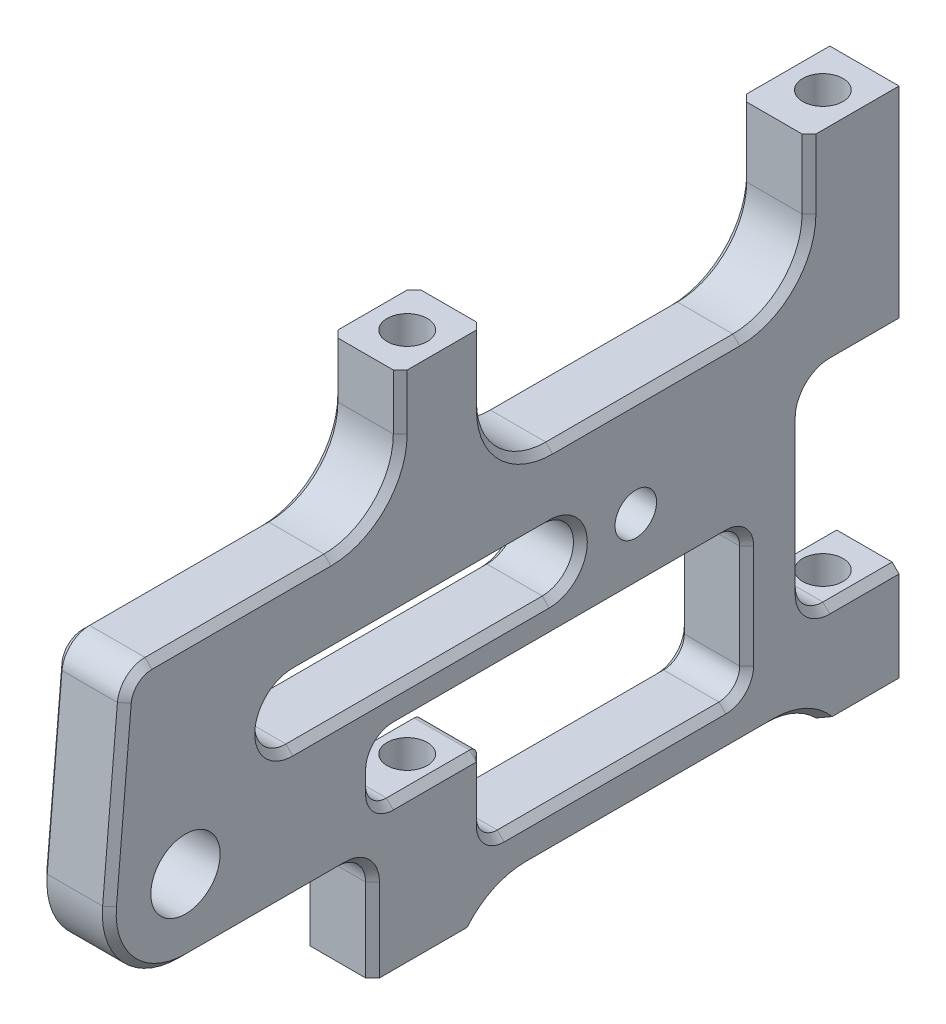
SolidWorks part; units mm, degrees
ref_plane "Front" through (0, 0, 0) normal (0, 0, 1) x (1, 0, 0)
ref_plane "Top" through (0, 0, 0) normal (0, 1, 0) x (1, 0, 0)
ref_plane "Right" through (0, 0, 0) normal (1, 0, 0) x (0, 0, -1)
sketch "Esquisse1" plane through (0, 0, 0) normal (1, 0, 0) x (0, 0, -1)
  line L1 (0, 0) -> (-57, 0)
  line L2 (0, 0) -> (0, 37)
  line L3 (0, 37) -> (-57, 37)
  line L4 (-57, 0) -> (-57, 37)
  dimension "D1" = 37
  dimension "D2" = 57
extrude "Boss.-Extru.1" add sketch "Esquisse1" along normal mid plane 5
sketch "Esquisse2" plane through (2.5, 0, 0) normal (1, 0, 0) x (0, 0, -1)
  line L0 (0, 0) -> (0, 37) construction
  line L1 (0, 7) -> (-7, 7)
  line L2 (0, 7) -> (0, 22)
  line L3 (0, 22) -> (-7, 22)
  line L4 (-7, 7) -> (-7, 22)
  line L5 (-57, 0) -> (0, 0) construction
  dimension "D1" = 15
  dimension "D2" = 7
  dimension "D3" = 7
extrude "Enlèv. mat.-Extru.1" cut sketch "Esquisse2" against normal through all
sketch "Esquisse3" plane through (2.5, 0, 0) normal (1, 0, 0) x (0, 0, -1)
  line L0 (0, 37) -> (-57, 37) construction
  line L1 (-6.5, 37) -> (-30, 37)
  line L2 (-6.5, 37) -> (-6.5, 27)
  line L3 (-6.5, 27) -> (-30, 27)
  line L4 (-30, 37) -> (-30, 27)
  line L5 (0, 22) -> (0, 37) construction
  dimension "D1" = 23.5
  dimension "D2" = 10
  dimension "D3" = 6.5
extrude "Enlèv. mat.-Extru.2" cut sketch "Esquisse3" against normal through all
sketch "Esquisse4" plane through (2.5, 0, 0) normal (1, 0, 0) x (0, 0, -1)
  line L0 (-30, 27) -> (-6.5, 27) construction
  line L1 (-57, 37) -> (-36, 37)
  line L2 (-57, 37) -> (-57, 28)
  line L3 (-57, 28) -> (-36, 28)
  line L4 (-36, 37) -> (-36, 28)
  line L5 (0, 22) -> (0, 37) construction
  dimension "D1" = 1
  dimension "D2" = 36
extrude "Enlèv. mat.-Extru.3" cut sketch "Esquisse4" against normal through all
sketch "Esquisse5" plane through (2.5, 0, 0) normal (1, 0, 0) x (0, 0, -1)
  line L0 (0, 0) -> (0, 7) construction
  line L1 (-57, 0) -> (-38, 0)
  line L2 (-57, 0) -> (-57, 8)
  line L3 (-57, 8) -> (-38, 8)
  line L4 (-38, 0) -> (-38, 8)
  dimension "D1" = 38
  dimension "D2" = 8
extrude "Enlèv. mat.-Extru.4" cut sketch "Esquisse5" against normal through all
sketch "Esquisse6" plane through (2.5, 0, 0) normal (1, 0, 0) x (0, 0, -1)
  line L0 (-38, 8) -> (-57, 8) construction
  line L1 (-51.5, 8) -> (-57, 8)
  line L2 (-57, 8) -> (-57, 28)
  line L3 (-57, 28) -> (-55.7524, 28)
  line L4 (-57, 28) -> (-36, 28) construction
  line L5 (-55.7524, 28) -> (-56.9791, 13.9794)
  arc A0 (-56.9791, 13.9794) -> (-51.5, 8) centre (-51.5, 13.5) ccw
  circle A1 centre (-51.5, 13.5) radius 2.5
  line M4 (-57, 8) -> (-38, 8)
  line M18 (-36, 28) -> (-57, 28)
  line M19 (-57, 28) -> (-57, 8)
  dimension "D2" = 11
  dimension "D3" = 5
  dimension "D1" = 5
extrude "Enlèv. mat.-Extru.5" cut sketch "Esquisse6" against normal blind 5 contours A0 L5 M18 M19 | A0 L2 M4 | A1
sketch "Esquisse7" plane through (2.5, 0, 0) normal (1, 0, 0) x (0, 0, -1)
  line L0 (-38, 15) -> (-11, 15)
  line L1 (-11, 15) -> (-11, 4.5)
  line L2 (-11, 4.5) -> (-30, 4.5)
  line L3 (-30, 4.5) -> (-30, 10.5)
  line L4 (-30, 10.5) -> (-38, 10.5)
  line L5 (-38, 10.5) -> (-38, 15)
  line L6 (0, 0) -> (0, 7) construction
  line L7 (-38, 0) -> (0, 0) construction
  dimension "D1" = 10.5
  dimension "D2" = 11
  dimension "D3" = 19
  dimension "D4" = 27
  dimension "D5" = 4.5
  dimension "D6" = 4.5
extrude "Enlèv. mat.-Extru.6" cut sketch "Esquisse7" against normal through all
sketch "Esquisse8" plane through (2.5, 0, 0) normal (1, 0, 0) x (0, 0, -1)
  line L0 (-43.75, 19.75) -> (-25.25, 19.75) construction
  line L1 (-43.75, 22) -> (-25.25, 22)
  line L2 (-43.75, 17.5) -> (-25.25, 17.5)
  line L3 (0, 22) -> (0, 37) construction
  line L4 (-30, 37) -> (-36, 37) construction
  arc A0 (-43.75, 22) -> (-43.75, 17.5) centre (-43.75, 19.75) ccw
  arc A1 (-25.25, 17.5) -> (-25.25, 22) centre (-25.25, 19.75) ccw
  circle A2 centre (-19, 19.75) radius 1.5
  point P2 (-34.5, 19.75)
  point P7 (-46, 19.75)
  point P8 (-23, 19.75)
  dimension "D5" = 3
  dimension "D1" = 23
  dimension "D2" = 23
  dimension "D3" = 4.5
  dimension "D4" = 15
  dimension "D6" = 4
extrude "Enlèv. mat.-Extru.7" cut sketch "Esquisse8" against normal through all
sketch "Esquisse9" plane through (2.5, 0, 0) normal (1, 0, 0) x (0, 0, -1)
  line L0 (-38, 0) -> (0, 0) construction
  line L1 (-30.5, 0) -> (-5.5, 0)
  line L2 (-30.5, 0) -> (-30.5, 1.5)
  line L3 (-30.5, 1.5) -> (-5.5, 1.5)
  line L4 (-5.5, 0) -> (-5.5, 1.5)
  line L5 (0, 0) -> (0, 7) construction
  dimension "D1" = 1.5
  dimension "D2" = 25
  dimension "D3" = 5.5
extrude "Enlèv. mat.-Extru.8" cut sketch "Esquisse9" against normal through all
fillet "Congé1" radius 5 5 edges at (0, 27, 30) (0, 28, 36) (0, 27, 6.5) (0, 1.5, 5.5) (0, 1.5, 30.5)
fillet "Congé2" radius 1.5 5 edges at (0, 15, 11) (0, 4.5, 11) (0, 4.5, 30) (0, 10.5, 38) (0, 15, 38)
fillet "Congé3" radius 0.5 1 edges at (0, 10.5, 30)
fillet "Congé4" radius 2 3 edges at (0, 8, 38) (0, 7, 7) (0, 22, 7)
fillet "Congé5" radius 2 1 edges at (0, 28, 55.7524)
hole_wizard "Trou taraudé M3.51" positions "Esquisse11" profile "Esquisse13" tap size "M3.5" standard "ISO"
sketch "Esquisse11" plane through (0, 0, 0) normal (0, -1, 0) x (-1, 0, 0)
  point P0 (0, -3)
  point P2 (0, -33)
  dimension "D1" = 3
  dimension "D2" = 30
sketch "Esquisse13" plane through (0, 0, 3) normal (1, 0, 0) x (0, 0, -1)
  line L0 (0, 0) -> (0, 12.8712)
  line L1 (0, 12.8712) -> (1.45, 12)
  line L2 (1.45, 12) -> (1.45, 0)
  line L5 (1.45, 0) -> (0, 0)
  line L10 (0, 12.8712) -> (-1.45, 12) construction
  line L11 (0, -6.35) -> (0, 107.95) construction
  dimension "Diamètre du trou pour taraudage" = 2.9
  dimension "Profondeur du trou pour taraudage" = 12
  dimension "Angle de pointe" = 118
cosmetic thread "Filetage de perçage1" parameters "D1"=10.5, "D2"=3.5
cosmetic thread "Filetage de perçage2" parameters "D1"=7, "D2"=3.5
hole_wizard "Trou taraudé M3.52" positions "Esquisse14" profile "Esquisse15" tap size "M3.5" standard "ISO"
sketch "Esquisse14" plane through (0, 37, 0) normal (0, 1, 0) x (1, 0, 0)
  line L0 (2.5, 0) -> (-2.5, 0) construction
  point P0 (0, -33)
  point P2 (0, -3)
  point P9 (0, 0)
  dimension "D1" = 30
  dimension "D2" = 3
sketch "Esquisse15" plane through (0, 37, 33) normal (1, 0, 0) x (0, 0, 1)
  line L0 (0, 0) -> (0, 10.8712)
  line L1 (0, 10.8712) -> (1.45, 10)
  line L2 (1.45, 10) -> (1.45, 0)
  line L5 (1.45, 0) -> (0, 0)
  line L10 (0, 10.8712) -> (-1.45, 10) construction
  line L11 (0, -6.35) -> (0, 107.95) construction
  dimension "Diamètre du trou pour taraudage" = 2.9
  dimension "Profondeur du trou pour taraudage" = 10
  dimension "Angle de pointe" = 118
cosmetic thread "Filetage de perçage3" parameters "D1"=10, "D2"=3.5
cosmetic thread "Filetage de perçage4" parameters "D1"=10, "D2"=3.5
chamfer "Chanfrein1" distance 0.5 angle 45 76 edges at (2.5, 22, 2.5) (2.5, 7, 2.5) (2.5, 21.4142, 6.4142) (2.5, 7.5858, 6.4142) (2.5, 14.5, 7) (2.5, 34.5, 6.5) (2.5, 28.4645, 7.9645) (2.5, 27, 18.25) (2.5, 28.4645, 28.5355) (2.5, 34.5, 30) (-2.5, 34.5, 30) (-2.5, 34.5, 6.5) (-2.5, 28.4645, 28.5355) (-2.5, 28.4645, 7.9645) (-2.5, 27, 18.25) (-2.5, 22, 2.5) (-2.5, 7, 2.5) (-2.5, 21.4142, 6.4142) (-2.5, 7.5858, 6.4142) (-2.5, 14.5, 7) (-2.5, 22, 34.5) (-2.5, 19.75, 46) (-2.5, 19.75, 23) (-2.5, 17.5, 34.5) (-2.5, 12.75, 38) (-2.5, 10.9393, 37.5607) (-2.5, 14.5607, 37.5607) (-2.5, 10.5, 33.5) (-2.5, 15, 24.5) (-2.5, 10.3536, 30.1464) (-2.5, 14.5607, 11.4393) (-2.5, 8, 30) (-2.5, 9.75, 11) (-2.5, 4.9393, 29.5607) (-2.5, 4.9393, 11.4393) (-2.5, 4.5, 20.5) (-2.5, 1.1098, 7.1342) (-2.5, 1.1098, 28.8658) (-2.5, 1.5, 18) (-2.5, 35, 36) (-2.5, 29.4645, 37.4645) (-2.5, 28, 47.4599) (-2.5, 27.4746, 55.2709) (-2.5, 20.0768, 56.4456) (-2.5, 9.7843, 55.555) (-2.5, 8, 45.75) (-2.5, 7.4142, 38.5858) (-2.5, 3, 38) (2.5, 35, 36) (2.5, 29.4645, 37.4645) (2.5, 28, 47.4599) (2.5, 27.4746, 55.2709) (2.5, 20.0768, 56.4456) (2.5, 9.7843, 55.555) (2.5, 8, 45.75) (2.5, 7.4142, 38.5858) (2.5, 3, 38) (2.5, 1.1098, 7.1342) (2.5, 1.5, 18) (2.5, 1.1098, 28.8658) (2.5, 4.9393, 11.4393) (2.5, 4.5, 20.5) (2.5, 9.75, 11) (2.5, 4.9393, 29.5607) (2.5, 14.5607, 11.4393) (2.5, 8, 30) (2.5, 15, 24.5) (2.5, 10.3536, 30.1464) (2.5, 14.5607, 37.5607) (2.5, 10.5, 33.5) (2.5, 12.75, 38) (2.5, 10.9393, 37.5607) (2.5, 22, 34.5) (2.5, 19.75, 46) (2.5, 19.75, 23) (2.5, 17.5, 34.5)
